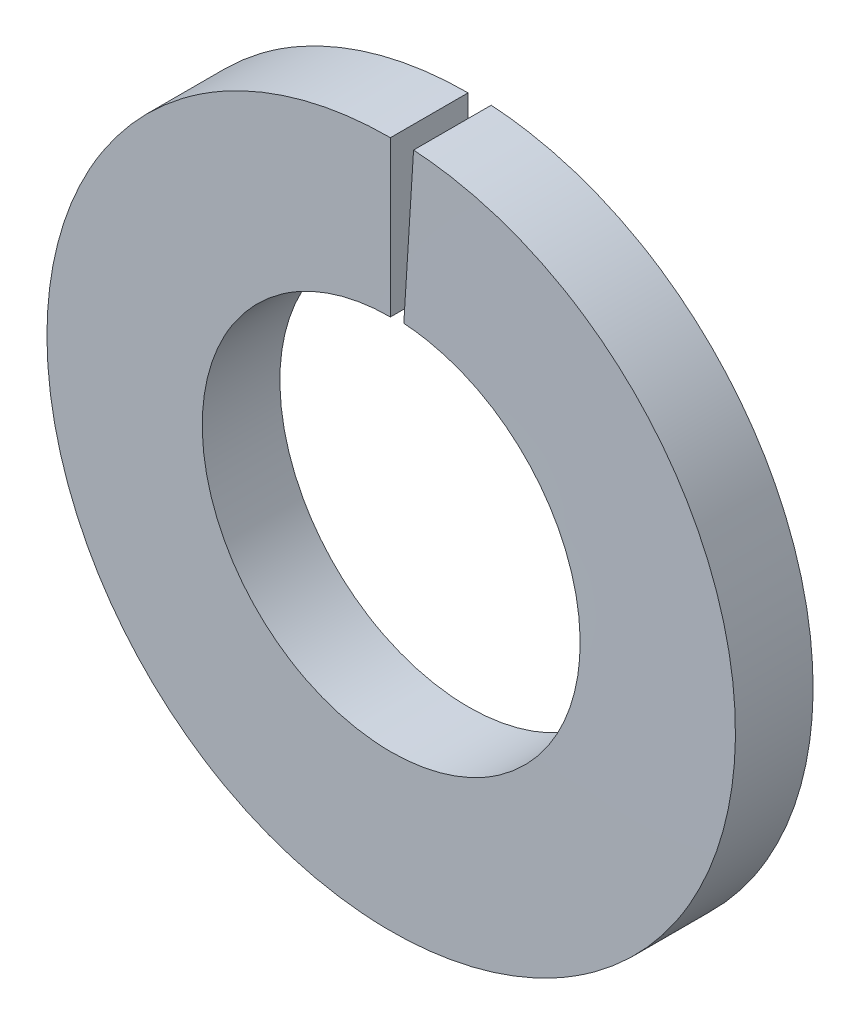
SolidWorks part; units mm, degrees
ref_plane "Front Plane" through (0, 0, 0) normal (0, 0, 1) x (1, 0, 0)
ref_plane "Top Plane" through (0, 0, 0) normal (0, 1, 0) x (1, 0, 0)
ref_plane "Right Plane" through (0, 0, 0) normal (1, 0, 0) x (0, 0, -1)
sketch "Sketch1" plane through (0, 0, 0) normal (0, 0, 1) x (1, 0, 0)
  line L0 (0, 3.1) -> (0, 1.7) construction
  circle A0 centre (0, 0) radius 3.1
  circle A1 centre (0, 0) radius 1.7 construction
  dimension "ID" = 3.4
  dimension "OD" = 6.2
curve "Helix/Spiral1" pitch 0.0141 height 0.014 radius 3.1 left hand yes centre (0, 0, 0) axis (0, 0, -1) start towards (0, 1, 0) parameters "HT"=0.014
sketch "Sketch2" plane through (0, 0, 0) normal (1, 0, 0) x (0, 0, -1)
  line L1 (0, 3.1) -> (-0.7, 3.1)
  line L2 (0, 3.1) -> (0, 1.7)
  line L3 (0, 1.7) -> (-0.7, 1.7)
  line L4 (-0.7, 3.1) -> (-0.7, 1.7)
  dimension "THK" = 0.7
sweep "Sweep1" add profiles "Sketch2" path "Helix/Spiral1"
equation "\"HT@Helix/Spiral1\" = \"THK@Sketch2\" * .02"
